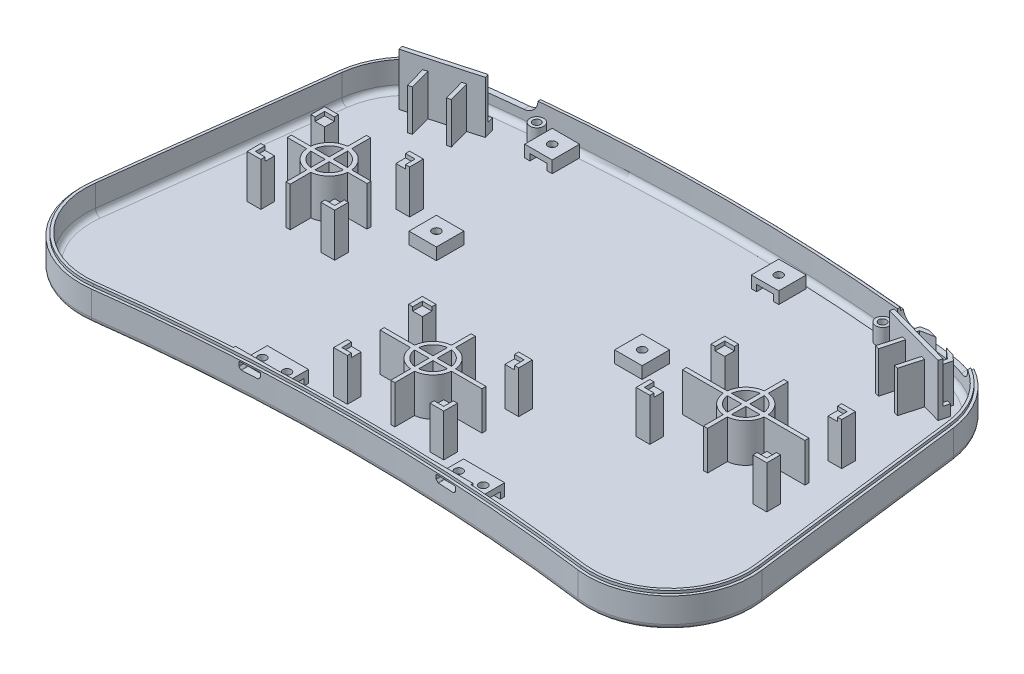
SolidWorks part; units mm, degrees
ref_plane "Plan de face" through (0, 0, 0) normal (0, 0, 1) x (1, 0, 0)
ref_plane "Plan de dessus" through (0, 0, 0) normal (0, 1, 0) x (1, 0, 0)
ref_plane "Plan de droite" through (0, 0, 0) normal (1, 0, 0) x (0, 0, -1)
sketch "Esquisse fond coque" plane through (0, 0, 0) normal (0, 1, 0) x (1, 0, 0)
  line L0 (-122.2671, -38.9175) -> (-112.2671, 40.8662)
  line L1 (112.2671, 40.8662) -> (122.2671, -38.9175)
  line L2 (-103.7302, 58.3314) -> (113.6596, -63.9151) construction
  line L3 (-113.6596, -63.9151) -> (103.7302, 58.3314) construction
  arc A0 (-112.2671, 40.8662) -> (-86.2786, 66.8963) centre (-82.5, 37.1352) cw
  arc A1 (-86.2786, 66.8963) -> (86.2786, 66.8963) centre (0, -612.6484) cw
  arc A2 (86.2786, 66.8963) -> (112.2671, 40.8662) centre (82.5, 37.1352) cw
  arc A3 (-122.2671, -38.9175) -> (-88.6189, -72.3963) centre (-92.5, -42.6484) ccw
  arc A4 (122.2671, -38.9175) -> (88.6189, -72.3963) centre (92.5, -42.6484) cw
  arc A5 (88.6189, -72.3963) -> (-88.6189, -72.3963) centre (0, -751.6398) ccw
  point P14 (122.5, -42.6484)
  point P15 (92.5, -72.6484)
  point P16 (-122.5, -42.6484)
  point P17 (0, 72.3516)
  point P18 (0, -66.6398)
  point P23 (0, 0)
  dimension "D4" = 30
  dimension "D5" = 30
  dimension "D6" = 685
  dimension "D7" = 685
  dimension "D1" = 245
  dimension "D2" = 165
  dimension "D3" = 145
extrude "Fond coque" add sketch "Esquisse fond coque" along normal blind 2
sketch "Esquisse contour coque" plane through (0, 2, 0) normal (0, 1, 0) x (1, 0, 0)
  line L0 (-120.2826, -39.1662) -> (-110.2826, 40.6174)
  line L1 (110.2826, 40.6174) -> (120.2826, -39.1662)
  line L2 (122.2671, -38.9175) -> (112.2671, 40.8662) construction
  line L3 (-112.2671, 40.8662) -> (-122.2671, -38.9175) construction
  line L4 (-122.2671, -38.9175) -> (-112.2671, 40.8662)
  line L5 (112.2671, 40.8662) -> (122.2671, -38.9175)
  arc A0 (-110.2826, 40.6174) -> (-86.0267, 64.9122) centre (-82.5, 37.1352) cw
  arc A1 (-86.0267, 64.9122) -> (86.0267, 64.9122) centre (0, -612.6484) cw
  arc A2 (86.0267, 64.9122) -> (110.2826, 40.6174) centre (82.5, 37.1352) cw
  arc A3 (120.2826, -39.1662) -> (88.8776, -70.4131) centre (92.5, -42.6484) cw
  arc A4 (-120.2826, -39.1662) -> (-88.8776, -70.4131) centre (-92.5, -42.6484) ccw
  arc A5 (-88.8776, -70.4131) -> (88.8776, -70.4131) centre (0, -751.6398) cw
  arc A6 (86.2786, 66.8963) -> (-86.2786, 66.8963) centre (0, -612.6484) ccw construction
  arc A7 (88.6189, -72.3963) -> (-88.6189, -72.3963) centre (0, -751.6398) ccw construction
  arc A8 (-88.6189, -72.3963) -> (-122.2671, -38.9175) centre (-92.5, -42.6484) cw
  arc A9 (-122.2671, -38.9175) -> (-88.6189, -72.3963) centre (-92.5, -42.6484) ccw construction
  arc A10 (88.6189, -72.3963) -> (122.2671, -38.9175) centre (92.5, -42.6484) ccw
  arc A11 (88.6189, -72.3963) -> (122.2671, -38.9175) centre (92.5, -42.6484) ccw construction
  arc A12 (-112.2671, 40.8662) -> (-86.2786, 66.8963) centre (-82.5, 37.1352) cw
  arc A13 (-86.2786, 66.8963) -> (-112.2671, 40.8662) centre (-82.5, 37.1352) ccw construction
  arc A14 (86.2786, 66.8963) -> (112.2671, 40.8662) centre (82.5, 37.1352) cw
  arc A15 (112.2671, 40.8662) -> (86.2786, 66.8963) centre (82.5, 37.1352) ccw construction
  arc A16 (-88.6189, -72.3963) -> (88.6189, -72.3963) centre (0, -751.6398) cw
  arc A17 (-86.2786, 66.8963) -> (86.2786, 66.8963) centre (0, -612.6484) cw
  point P6 (0, 70.3516)
  point P14 (0, -64.6398)
  point P18 (0, 72.3516)
  point P23 (0, -66.6398)
  point P31 (-113.6596, -63.9151)
  point P36 (-113.6596, -63.9151)
  point P37 (0, -66.6398)
  point P39 (113.6596, -63.9151)
  point P45 (113.6596, -63.9151)
  point P54 (-103.7302, 58.3314)
  point P55 (-103.7302, 58.3314)
  point P58 (103.7302, 58.3314)
  point P64 (103.7302, 58.3314)
  point P66 (0, 72.3516)
  dimension "D1" = 2
  dimension "D2" = 2
  dimension "D3" = 2
  dimension "D4" = 2
extrude "Contour coque" add sketch "Esquisse contour coque" along normal blind 10
fillet "Congé1" radius 2 8 edges at (-115.2826, 2, -0.7256) (-102.3148, 2, -56.9183) (0, 2, -70.3516) (102.3148, 2, -56.9183) (115.2826, 2, -0.7256) (112.249, 2, 62.4973) (0, 2, 64.6398) (-112.249, 2, 62.4973)
fillet "Congé2" radius 2 8 edges at (0, 0, 66.6398) (113.6596, 0, 63.9151) (117.2671, 0, -0.9743) (103.7302, 0, -58.3314) (0, 0, -72.3516) (-103.7302, 0, -58.3314) (-117.2671, 0, -0.9743) (-113.6596, 0, 63.9151)
sketch "Esquisse glissières Arduino Due" plane through (0, 2, 0) normal (0, 1, 0) x (1, 0, 0)
  line L4 (23.1981, 13.3602) -> (24.7481, 10.6755)
  line L5 (24.7481, 10.6755) -> (27.8481, 10.6755)
  line L6 (27.8481, 10.6755) -> (29.3981, 13.3602)
  line L10 (-51.7319, 13.3602) -> (-50.1819, 10.6755)
  line L11 (-50.1819, 10.6755) -> (-47.0819, 10.6755)
  line L12 (-47.0819, 10.6755) -> (-45.5319, 13.3602)
  line L13 (-51.8819, 61.8802) -> (-53.4319, 64.5649)
  line L14 (-53.4319, 64.5649) -> (-56.5319, 64.5649)
  line L15 (-56.5319, 64.5649) -> (-58.0819, 61.8802)
  line L19 (30.6681, 61.8802) -> (29.1181, 64.5649)
  line L20 (29.1181, 64.5649) -> (26.0181, 64.5649)
  line L21 (26.0181, 64.5649) -> (24.4681, 61.8802)
  line L25 (-45.5319, 13.3602) -> (-45.5319, 18.3602)
  line L26 (23.1981, 13.3602) -> (23.1981, 18.3602)
  line L27 (-25.6887, 16.0449) -> (-27.2475, 16.0449) [skipped]
  line L28 (-43.7885, 10.3406) -> (-44.5679, 11.6906) [skipped]
  line L29 (-41.86, 30.4587) -> (-42.6394, 29.1087) [skipped]
  line L36 (29.3981, 13.3602) -> (29.3981, 18.3602)
  line L37 (-51.8819, 61.8802) -> (-51.8819, 56.8802)
  line L38 (-58.0819, 61.8802) -> (-58.0819, 56.8802)
  line L39 (24.4681, 61.8802) -> (24.4681, 56.8802)
  line L40 (49.2413, 16.0449) -> (47.6825, 16.0449) [skipped]
  line L41 (-9.0051, 79.8766) -> (-9.7845, 81.2266) [skipped]
  line L42 (72.9294, 99.4972) -> (72.15, 98.1472) [skipped]
  line L43 (-7.7887, 59.1955) -> (-6.2299, 59.1955) [skipped]
  line L44 (-49.1973, 66.53) -> (-48.4179, 67.88) [skipped]
  line L45 (-61.0747, 67.0639) -> (-60.2953, 65.7139) [skipped]
  line L46 (30.6681, 61.8802) -> (30.6681, 56.8802)
  line L47 (-54.9819, 61.8802) -> (27.5681, 61.8802) construction
  line L48 (48.6344, 59.1955) -> (50.1932, 59.1955) [skipped]
  line L49 (58.7941, 110.5957) -> (59.5735, 111.9457) [skipped]
  line L50 (6.7317, 92.6006) -> (7.5112, 91.2506) [skipped]
  line L51 (-48.6319, 13.3602) -> (26.2981, 13.3602) construction
  line L52 (-58.0819, 56.8802) -> (-59.9819, 56.8802)
  line L53 (-51.7319, 13.3602) -> (-51.7319, 18.3602)
  line L54 (-59.9819, 56.8802) -> (-59.9819, 66.8802)
  line L55 (-59.9819, 66.8802) -> (-49.9819, 66.8802)
  line L56 (-49.9819, 66.8802) -> (-49.9819, 56.8802)
  line L57 (-49.9819, 56.8802) -> (-51.8819, 56.8802)
  line L58 (24.4681, 56.8802) -> (22.5681, 56.8802)
  line L59 (22.5681, 56.8802) -> (22.5681, 66.8802)
  line L60 (22.5681, 66.8802) -> (32.5681, 66.8802)
  line L61 (32.5681, 66.8802) -> (32.5681, 56.8802)
  line L62 (32.5681, 56.8802) -> (30.6681, 56.8802)
  line L63 (23.1981, 18.3602) -> (21.2981, 18.3602)
  line L64 (21.2981, 18.3602) -> (21.2981, 8.3602)
  line L65 (21.2981, 8.3602) -> (31.2981, 8.3602)
  line L66 (31.2981, 8.3602) -> (31.2981, 18.3602)
  line L67 (31.2981, 18.3602) -> (29.3981, 18.3602)
  line L68 (-45.5319, 18.3602) -> (-43.6319, 18.3602)
  line L69 (-43.6319, 18.3602) -> (-43.6319, 8.3602)
  line L70 (-43.6319, 8.3602) -> (-53.6319, 8.3602)
  line L71 (-53.6319, 8.3602) -> (-53.6319, 18.3602)
  line L72 (-53.6319, 18.3602) -> (-51.7319, 18.3602)
  arc A0 (89.1364, -68.4299) -> (-89.1364, -68.4299) centre (0, -751.6398) ccw construction
  point P9 (-48.6319, 10.6755)
  point P30 (0, -62.6398)
  dimension "D4" = 5
  dimension "D8" = 5
  dimension "D10" = 5
  dimension "D12" = 5
  dimension "D2" = 1.27
  dimension "D3" = 92
  dimension "D5" = 6.2
  dimension "D6" = 74.93
  dimension "D7" = 3.1
  dimension "D9" = 6.2
  dimension "D11" = 82.55
  dimension "D13" = 76
  dimension "D14" = 6.2
  dimension "D15" = 6.2
  dimension "D16" = 48.52
  dimension "D17" = 10
  dimension "D18" = 10
  dimension "D19" = 10
  dimension "D20" = 10
  dimension "D21" = 10
  dimension "D22" = 10
  dimension "D23" = 10
  dimension "D24" = 10
  dimension "D25" = 10
extrude "Glissières Arduino Due" add sketch "Esquisse glissières Arduino Due" along normal blind 2.35
sketch "Esquisse support Arduino Due" plane through (0, 4.35, 0) normal (0, 1, 0) x (1, 0, 0)
  line L0 (-56.5319, 64.5649) -> (-53.4319, 64.5649) construction
  line L1 (-59.9819, 56.8802) -> (-49.9819, 56.8802)
  line L2 (-59.9819, 56.8802) -> (-59.9819, 66.8802)
  line L3 (-59.9819, 66.8802) -> (-49.9819, 66.8802)
  line L4 (-49.9819, 56.8802) -> (-49.9819, 66.8802)
  line L5 (22.5681, 56.8802) -> (32.5681, 56.8802)
  line L6 (22.5681, 56.8802) -> (22.5681, 66.8802)
  line L7 (22.5681, 66.8802) -> (32.5681, 66.8802)
  line L8 (32.5681, 56.8802) -> (32.5681, 66.8802)
  line L9 (21.2981, 8.3602) -> (31.2981, 8.3602)
  line L10 (21.2981, 8.3602) -> (21.2981, 18.3602)
  line L11 (21.2981, 18.3602) -> (31.2981, 18.3602)
  line L12 (31.2981, 8.3602) -> (31.2981, 18.3602)
  line L13 (-53.6319, 8.3602) -> (-43.6319, 8.3602)
  line L14 (-53.6319, 8.3602) -> (-53.6319, 18.3602)
  line L15 (-53.6319, 18.3602) -> (-43.6319, 18.3602)
  line L16 (-43.6319, 8.3602) -> (-43.6319, 18.3602)
  line L17 (-47.0819, 10.6755) -> (-50.1819, 10.6755) construction
  line L18 (27.8481, 10.6755) -> (24.7481, 10.6755) construction
  line L19 (26.0181, 64.5649) -> (29.1181, 64.5649) construction
  circle A2 centre (26.2981, 13.3602) radius 1.5
  circle A5 centre (27.5681, 61.8802) radius 1.5
  circle A6 centre (-48.6319, 13.3602) radius 1.5
  circle A7 centre (-54.9819, 61.8802) radius 1.5
  point P38 (-54.9819, 64.5649)
  point P41 (-48.6319, 10.6755)
  point P44 (26.2981, 10.6755)
  point P47 (27.5681, 64.5649)
  dimension "D1" = 3
  dimension "D2" = 3
  dimension "D3" = 3
  dimension "D4" = 3
extrude "Support Arduino Due" add sketch "Esquisse support Arduino Due" along normal blind 2
sketch "Esquisse entrée USB Native" plane through (0, 0, 0) normal (0, 0, 1) x (1, 0, 0)
  line L0 (32.925, 8) -> (38.575, 8)
  line L1 (38.7863, 8.087) -> (39.4113, 8.707)
  line L2 (39.5, 8.92) -> (39.5, 10.15)
  line L3 (39.2, 10.45) -> (32.3, 10.45)
  line L4 (32, 10.15) -> (32, 8.92)
  line L5 (32.0887, 8.707) -> (32.7137, 8.087)
  line L7 (-88.6189, 2) -> (88.6189, 2) construction
  arc A0 (38.575, 8) -> (38.7863, 8.087) centre (38.575, 8.3) ccw
  arc A1 (39.4113, 8.707) -> (39.5, 8.92) centre (39.2, 8.92) ccw
  arc A2 (39.5, 10.15) -> (39.2, 10.45) centre (39.2, 10.15) ccw
  arc A3 (32.3, 10.45) -> (32, 10.15) centre (32.3, 10.15) ccw
  arc A4 (32, 8.92) -> (32.0887, 8.707) centre (32.3, 8.92) ccw
  arc A5 (32.7137, 8.087) -> (32.925, 8) centre (32.925, 8.3) ccw
  point P20 (35.75, 8)
  point P42 (35.75, 10.45)
  dimension "D2" = 0.3
  dimension "D3" = 0.3
  dimension "D4" = 0.3
  dimension "D5" = 0.3
  dimension "D6" = 0.3
  dimension "D7" = 0.3
  dimension "D1" = 2.45
  dimension "D8" = 5.65
  dimension "D9" = 0.92
  dimension "D10" = 32
  dimension "D12" = 7.5
  dimension "D13" = 8.45
extrude "Entrée USB Native" cut sketch "Esquisse entrée USB Native" along normal up to next
sketch "Esquisse glissières USB Native" plane through (0, 2, 0) normal (0, 1, 0) x (1, 0, 0)
  line L0 (28.2503, -53.6426) -> (28.2503, -55.2409)
  line L1 (28.2503, -53.6426) -> (43.2503, -53.6426)
  line L2 (43.2503, -53.6426) -> (43.2503, -55.2409)
  line L3 (33.86, -58.3409) -> (37.4406, -58.3409) construction
  line L7 (31.1753, -61.4409) -> (33.86, -59.8909)
  line L8 (33.86, -59.8909) -> (33.86, -56.7909)
  line L9 (33.86, -56.7909) -> (31.1753, -55.2409)
  line L10 (40.1253, -55.2409) -> (37.4406, -56.7909)
  line L11 (37.4406, -56.7909) -> (37.4406, -59.8909)
  line L12 (37.4406, -59.8909) -> (40.1253, -61.4409)
  line L16 (31.1753, -55.2409) -> (28.2503, -55.2409)
  line L17 (31.1753, -61.4409) -> (28.2503, -61.4409)
  line L18 (28.2503, -61.4409) -> (28.2503, -65.2209)
  line L22 (40.1253, -55.2409) -> (43.2503, -55.2409)
  line L23 (40.1253, -61.4409) -> (43.2503, -61.4409)
  line L25 (28.9014, -67.921) -> (30.2437, -67.146) [skipped]
  line L26 (43.2503, -61.4409) -> (43.2503, -66.0026)
  line L27 (42.81, -66.5249) -> (42.81, -64.9749) [skipped]
  line L28 (32.0932, -50.6036) -> (30.7509, -49.8286) [skipped]
  arc A0 (88.8776, -70.4131) -> (-88.8776, -70.4131) centre (0, -751.6398) ccw construction
  arc A2 (88.8776, -70.4131) -> (-88.8776, -70.4131) centre (0, -751.6398) ccw construction
  arc A3 (28.2503, -65.2209) -> (43.2503, -66.0026) centre (0, -751.6398) cw
  arc A5 (38.575, -65.7237) -> (32.925, -65.4292) centre (0, -751.6398) ccw construction
  point P11 (35.7503, -53.6426)
  point P13 (40.1253, -58.3409)
  point P14 (31.1753, -58.3409)
  point P27 (35.6503, -58.3409)
  point P31 (35.7503, -65.5706)
  dimension "D1" = 12.36
  dimension "D2" = 6.88
  dimension "D3" = 6.2
  dimension "D4" = 8.95
  dimension "D5" = 15
  dimension "D6" = 0.1
  dimension "D7" = 0.1
extrude "Glissières USB Native" add sketch "Esquisse glissières USB Native" along normal blind 2.35
sketch "Esquisse support USB Native" plane through (0, 4.35, 0) normal (0, 1, 0) x (1, 0, 0)
  line L0 (28.2503, -53.6426) -> (43.2503, -53.6426)
  line L1 (43.2503, -53.6426) -> (43.2503, -66.0026)
  line L2 (28.2503, -53.6426) -> (28.2503, -65.2209)
  line L3 (33.86, -56.7909) -> (33.86, -59.8909) construction
  line L4 (37.4406, -59.8909) -> (37.4406, -56.7909) construction
  arc A0 (28.2503, -65.2209) -> (43.2503, -66.0026) centre (0, -751.6398) cw
  arc A1 (43.2503, -66.0026) -> (28.2503, -65.2209) centre (0, -751.6398) ccw construction
  circle A2 centre (31.1753, -58.3409) radius 1.5
  circle A3 centre (40.1253, -58.3409) radius 1.5
  point P17 (33.86, -58.3409)
  point P23 (37.4406, -58.3409)
  dimension "D1" = 3
  dimension "D2" = 3
extrude "Support USB Native" add sketch "Esquisse support USB Native" along normal blind 2.05
sketch "Esquisse4" plane through (0, 6.4, 0) normal (0, 1, 0) x (1, 0, 0)
  line L0 (28.2503, -65.2209) -> (43.2503, -65.2209)
  line L1 (43.2503, -66.0026) -> (43.2503, -53.6426) construction
  line L2 (43.2503, -65.2209) -> (43.2503, -66.0026)
  line L6 (28.2503, -53.6426) -> (28.2503, -65.2209)
  line L7 (43.2503, -66.0026) -> (43.2503, -53.6426)
  line L8 (43.2503, -53.6426) -> (28.2503, -53.6426)
  arc A1 (43.2503, -66.0026) -> (28.2503, -65.2209) centre (0, -751.6398) ccw
  arc A2 (43.2503, -66.0026) -> (28.2503, -65.2209) centre (0, -751.6398) ccw
  dimension "D1" = 0
extrude "Boss.-Extru.4" add sketch "Esquisse4" along normal blind 5.6
sketch "Esquisse coins DPad" plane through (0, 2, 0) normal (0, 1, 0) x (1, 0, 0)
  line L0 (-95.2981, 15.8201) -> (-95.2981, 19.3201)
  line L1 (-96.7981, 20.8201) -> (-91.7981, 20.8201)
  line L2 (-96.7981, 20.8201) -> (-96.7981, 15.8201)
  line L3 (-96.7981, 15.8201) -> (-95.2981, 15.8201)
  line L4 (-91.7981, 20.8201) -> (-91.7981, 19.3201)
  line L9 (-96.7981, -2.4299) -> (-95.2981, -2.4299)
  line L10 (-96.7981, -2.4299) -> (-96.7981, -7.4299)
  line L11 (-96.7981, -7.4299) -> (-91.7981, -7.4299)
  line L12 (-91.7981, -5.9299) -> (-91.7981, -7.4299)
  line L13 (-62.2981, -10.0299) -> (-67.2981, -10.0299)
  line L14 (-62.2981, -10.0299) -> (-62.2981, -5.0299)
  line L15 (-62.2981, -5.0299) -> (-63.7981, -5.0299)
  line L16 (-67.2981, -10.0299) -> (-67.2981, -8.5299)
  line L17 (-95.2981, 19.3201) -> (-91.7981, 19.3201)
  line L19 (-62.2981, 22.2701) -> (-67.2981, 22.2701)
  line L20 (-95.2981, -2.4299) -> (-95.2981, -5.9299)
  line L21 (-95.2981, -5.9299) -> (-91.7981, -5.9299)
  line L22 (-63.7981, -5.0299) -> (-63.7981, -8.5299)
  line L23 (-63.7981, -8.5299) -> (-67.2981, -8.5299)
  line L24 (-62.2981, 22.2701) -> (-62.2981, 17.2701)
  line L25 (-62.2981, 17.2701) -> (-63.7981, 17.2701)
  line L26 (-67.2981, 22.2701) -> (-67.2981, 20.7701)
  line L29 (-67.2981, 20.7701) -> (-63.7981, 20.7701)
  line L30 (-63.7981, 17.2701) -> (-63.7981, 20.7701)
  dimension "D2" = 1.5
  dimension "D3" = 1.5
  dimension "D4" = 1.5
  dimension "D5" = 1.5
  dimension "D6" = 1.5
  dimension "D7" = 1.5
  dimension "D8" = 1.5
  dimension "D9" = 1.5
  dimension "D10" = 31.5
  dimension "D11" = 2.6
  dimension "D12" = 5
  dimension "D13" = 5
  dimension "D14" = 5
  dimension "D15" = 5
  dimension "D16" = 5
  dimension "D17" = 5
  dimension "D18" = 1.45
  dimension "D19" = 5
  dimension "D20" = 5
  dimension "D21" = 29.3
  dimension "D22" = 61
  dimension "D23" = 21.5
sketch "Esquisse intérieur DPad" plane through (0, 2, 0) normal (0, 1, 0) x (1, 0, 0)
  line L0 (-91.7981, 15.8201) -> (-67.2981, -5.0299) construction
  line L1 (-95.2981, 19.3201) -> (-91.7981, 19.3201)
  line L2 (-95.2981, 19.3201) -> (-95.2981, 15.8201)
  line L3 (-95.2981, 15.8201) -> (-91.7981, 15.8201)
  line L4 (-91.7981, 19.3201) -> (-91.7981, 15.8201)
  line L5 (-63.7981, 20.7701) -> (-67.2981, 20.7701)
  line L6 (-63.7981, 20.7701) -> (-63.7981, 17.2701)
  line L7 (-63.7981, 17.2701) -> (-67.2981, 17.2701)
  line L8 (-67.2981, 20.7701) -> (-67.2981, 17.2701)
  line L9 (-95.2981, -5.9299) -> (-91.7981, -5.9299)
  line L10 (-95.2981, -5.9299) -> (-95.2981, -2.4299)
  line L11 (-95.2981, -2.4299) -> (-91.7981, -2.4299)
  line L12 (-91.7981, -5.9299) -> (-91.7981, -2.4299)
  line L13 (-63.7981, -8.5299) -> (-67.2981, -8.5299)
  line L14 (-63.7981, -8.5299) -> (-63.7981, -5.0299)
  line L15 (-63.7981, -5.0299) -> (-67.2981, -5.0299)
  line L16 (-67.2981, -8.5299) -> (-67.2981, -5.0299)
  line L21 (-80.0216, 5.6863) -> (-66.2451, 5.6863)
  line L22 (-81.5216, -8.5299) -> (-80.0216, -8.5299)
  line L23 (-91.7981, -2.4299) -> (-67.2981, 17.2701) construction
  line L24 (-81.5216, -8.5299) -> (-81.5216, 5.6863)
  line L25 (-81.5216, 20.7701) -> (-80.0216, 20.7701)
  line L26 (-80.0216, -8.5299) -> (-80.0216, 5.6863)
  line L27 (-81.5216, 7.1863) -> (-80.0216, 7.1863) construction
  line L29 (-95.2981, 7.1863) -> (-81.5216, 7.1863)
  line L30 (-95.2981, 7.1863) -> (-95.2981, 5.6863)
  line L31 (-95.2981, 5.6863) -> (-81.5216, 5.6863)
  line L32 (-66.2451, 7.1863) -> (-66.2451, 5.6863)
  line L33 (-95.2981, 7.1863) -> (-66.2451, 5.6863) construction
  line L34 (-95.2981, 5.6863) -> (-66.2451, 7.1863) construction
  line L35 (-80.0216, 7.1863) -> (-80.0216, 20.7701)
  line L36 (-81.5216, 7.1863) -> (-81.5216, 20.7701)
  line L37 (-80.0216, 7.1863) -> (-66.2451, 7.1863)
  point P24 (-80.7716, 6.4363)
  point P29 (-80.7716, 6.4363)
  point P34 (-80.7716, 6.4363)
  point P39 (-80.7716, 7.1863)
  dimension "D1" = 1.5
  dimension "D2" = 1.5
extrude "Coins DPad" add sketch "Esquisse coins DPad" along normal blind 15.8
extrude "Intérieur DPad" add sketch "Esquisse intérieur DPad" along normal blind 14.4
sketch "Esquisse cercle DPad" plane through (0, 2, 0) normal (0, 1, 0) x (1, 0, 0)
  circle A0 centre (-80.7716, 6.4363) radius 6
  circle A1 centre (-80.7716, 6.4363) radius 7.5
  dimension "D1" = 12
  dimension "D2" = 15
extrude "Cercle DPad" add sketch "Esquisse cercle DPad" along normal blind 14.4
sketch "Esquisse coins ABXY" plane through (0, 2, 0) normal (0, 1, 0) x (1, 0, 0)
  line L1 (48.1981, 16.5851) -> (49.6981, 16.5851)
  line L2 (48.1981, 16.5851) -> (48.1981, 21.5851)
  line L3 (48.1981, 21.5851) -> (53.1981, 21.5851)
  line L4 (53.1981, 20.0851) -> (53.1981, 21.5851)
  line L7 (53.1981, 20.0851) -> (49.6981, 20.0851)
  line L8 (49.6981, 16.5851) -> (49.6981, 20.0851)
  line L9 (94.2981, 16.5851) -> (95.7981, 16.5851)
  line L10 (90.7981, 20.0851) -> (90.7981, 21.5851)
  line L11 (90.7981, 21.5851) -> (95.7981, 21.5851)
  line L12 (95.7981, 16.5851) -> (95.7981, 21.5851)
  line L15 (90.7981, 20.0851) -> (94.2981, 20.0851)
  line L16 (94.2981, 16.5851) -> (94.2981, 20.0851)
  line L17 (49.6981, -5.7149) -> (48.1981, -5.7149)
  line L18 (53.1981, -9.2149) -> (53.1981, -10.7149)
  line L19 (53.1981, -10.7149) -> (48.1981, -10.7149)
  line L20 (48.1981, -5.7149) -> (48.1981, -10.7149)
  line L23 (53.1981, -9.2149) -> (49.6981, -9.2149)
  line L24 (49.6981, -5.7149) -> (49.6981, -9.2149)
  line L25 (94.2981, -5.7149) -> (95.7981, -5.7149)
  line L26 (90.7981, -9.2149) -> (90.7981, -10.7149)
  line L27 (90.7981, -10.7149) -> (95.7981, -10.7149)
  line L28 (95.7981, -5.7149) -> (95.7981, -10.7149)
  line L31 (90.7981, -9.2149) -> (94.2981, -9.2149)
  line L32 (94.2981, -5.7149) -> (94.2981, -9.2149)
  dimension "D1" = 1.5
  dimension "D2" = 1.5
  dimension "D3" = 1.5
  dimension "D4" = 1.5
  dimension "D5" = 1.5
  dimension "D6" = 1.5
  dimension "D7" = 1.5
  dimension "D8" = 1.5
  dimension "D9" = 44.6
  dimension "D10" = 29.3
  dimension "D11" = 5
  dimension "D12" = 5
  dimension "D13" = 5
  dimension "D14" = 5
  dimension "D15" = 57.715
  dimension "D16" = 5
  dimension "D17" = 5
  dimension "D18" = 5
  dimension "D19" = 22.5
  dimension "D20" = 5
extrude "Coins ABXY" add sketch "Esquisse coins ABXY" along normal blind 15.5
sketch "Esquisse intérieur ABXY" plane through (0, 2, 0) normal (0, 1, 0) x (1, 0, 0)
  line L0 (53.1981, 20.0851) -> (53.1981, 21.5851) construction
  line L1 (49.6981, 20.0851) -> (53.1981, 20.0851)
  line L2 (49.6981, 20.0851) -> (49.6981, 16.5851)
  line L3 (49.6981, 16.5851) -> (53.1981, 16.5851)
  line L4 (53.1981, 20.0851) -> (53.1981, 16.5851)
  line L5 (94.2981, 20.0851) -> (90.7981, 20.0851)
  line L6 (94.2981, 20.0851) -> (94.2981, 16.5851)
  line L7 (94.2981, 16.5851) -> (90.7981, 16.5851)
  line L8 (90.7981, 20.0851) -> (90.7981, 16.5851)
  line L9 (49.6981, -9.2149) -> (53.1981, -9.2149)
  line L10 (49.6981, -9.2149) -> (49.6981, -5.7149)
  line L11 (49.6981, -5.7149) -> (53.1981, -5.7149)
  line L12 (53.1981, -9.2149) -> (53.1981, -5.7149)
  line L13 (94.2981, -9.2149) -> (90.7981, -9.2149)
  line L14 (94.2981, -9.2149) -> (94.2981, -5.7149)
  line L15 (94.2981, -5.7149) -> (90.7981, -5.7149)
  line L16 (90.7981, -9.2149) -> (90.7981, -5.7149)
  line L17 (48.1981, 16.5851) -> (49.6981, 16.5851) construction
  line L18 (90.7981, 20.0851) -> (90.7981, 21.5851) construction
  line L19 (94.2981, 16.5851) -> (95.7981, 16.5851) construction
  line L20 (72.7481, 4.6851) -> (94.2981, 4.6851)
  line L21 (94.2981, -5.7149) -> (95.7981, -5.7149) construction
  line L22 (90.7981, -9.2149) -> (90.7981, -10.7149) construction
  line L23 (53.1981, -9.2149) -> (53.1981, -10.7149) construction
  line L24 (49.6981, -5.7149) -> (48.1981, -5.7149) construction
  line L25 (49.6981, 20.0851) -> (94.2981, -9.2149) construction
  line L30 (72.7481, -9.2149) -> (71.2481, -9.2149)
  line L31 (72.7481, -9.2149) -> (72.7481, 4.6851)
  line L32 (94.2981, 20.0851) -> (49.6981, -9.2149) construction
  line L33 (72.7481, 20.0851) -> (71.2481, 20.0851)
  line L34 (71.2481, -9.2149) -> (71.2481, 4.6851)
  line L35 (72.7481, -9.2149) -> (71.2481, 20.0851) construction
  line L36 (72.7481, 20.0851) -> (71.2481, -9.2149) construction
  line L37 (49.6981, 4.6851) -> (71.2481, 4.6851)
  line L38 (49.6981, 4.6851) -> (49.6981, 6.1851)
  line L39 (49.6981, 6.1851) -> (71.2481, 6.1851)
  line L40 (94.2981, 4.6851) -> (94.2981, 6.1851)
  line L41 (49.6981, 4.6851) -> (94.2981, 6.1851) construction
  line L42 (49.6981, 6.1851) -> (94.2981, 4.6851) construction
  line L43 (71.2481, 6.1851) -> (71.2481, 20.0851)
  line L44 (72.7481, 6.1851) -> (94.2981, 6.1851)
  line L45 (72.7481, 6.1851) -> (72.7481, 20.0851)
  point P36 (71.9981, 5.4351)
  point P37 (71.9981, 5.4351)
  point P41 (71.9981, 5.4351)
  point P43 (71.9981, 5.4351)
  dimension "D1" = 1.5
  dimension "D2" = 1.5
extrude "Intérieur ABXY" add sketch "Esquisse intérieur ABXY" along normal blind 14.1
sketch "Esquisse cercle ABXY" plane through (0, 2, 0) normal (0, 1, 0) x (1, 0, 0)
  circle A0 centre (71.9981, 5.4351) radius 6
  circle A1 centre (71.9981, 5.4351) radius 7.5
  dimension "D1" = 12
  dimension "D2" = 15
extrude "Cercle ABXY" add sketch "Esquisse cercle ABXY" along normal blind 14.1
sketch "Esquisse1" plane through (0, 2, 0) normal (0, 1, 0) x (1, 0, 0)
  line L0 (-18.05, -22.35) -> (19.05, -51.65) construction
  line L1 (-19.55, -20.85) -> (-14.55, -20.85)
  line L2 (-19.55, -20.85) -> (-19.55, -25.85)
  line L3 (-19.55, -25.85) -> (-18.05, -25.85)
  line L4 (-14.55, -20.85) -> (-14.55, -22.35)
  line L5 (15.55, -20.85) -> (20.55, -20.85)
  line L6 (15.55, -20.85) -> (15.55, -22.35)
  line L7 (19.05, -25.85) -> (20.55, -25.85)
  line L8 (20.55, -20.85) -> (20.55, -25.85)
  line L9 (-19.55, -53.15) -> (-14.55, -53.15)
  line L10 (-19.55, -53.15) -> (-19.55, -48.15)
  line L11 (-19.55, -48.15) -> (-18.05, -48.15)
  line L12 (-14.55, -53.15) -> (-14.55, -51.65)
  line L13 (20.55, -53.15) -> (15.55, -53.15)
  line L14 (20.55, -53.15) -> (20.55, -48.15)
  line L15 (20.55, -48.15) -> (19.05, -48.15)
  line L16 (15.55, -53.15) -> (15.55, -51.65)
  line L19 (-14.55, -51.65) -> (-18.05, -51.65)
  line L20 (-18.05, -48.15) -> (-18.05, -51.65)
  line L23 (-14.55, -22.35) -> (-18.05, -22.35)
  line L24 (-18.05, -25.85) -> (-18.05, -22.35)
  line L27 (15.55, -22.35) -> (19.05, -22.35)
  line L28 (19.05, -25.85) -> (19.05, -22.35)
  line L31 (15.55, -51.65) -> (19.05, -51.65)
  line L32 (19.05, -48.15) -> (19.05, -51.65)
  line L33 (-18.05, -51.65) -> (19.05, -22.35) construction
  point P1 (0.5, -37)
  dimension "D1" = 1.5
  dimension "D2" = 1.5
  dimension "D3" = 1.5
  dimension "D4" = 1.5
  dimension "D5" = 1.5
  dimension "D6" = 1.5
  dimension "D7" = 1.5
  dimension "D8" = 1.5
  dimension "D9" = 37.1
  dimension "D10" = 29.3
  dimension "D11" = 5
  dimension "D12" = 5
  dimension "D13" = 5
  dimension "D14" = 5
  dimension "D15" = 5
  dimension "D16" = 5
  dimension "D17" = 5
  dimension "D18" = 5
  dimension "D19" = 37
  dimension "D20" = 0.5
sketch "Esquisse2" plane through (0, 2, 0) normal (0, 1, 0) x (1, 0, 0)
  line L0 (-19.55, -25.85) -> (-18.05, -25.85) construction
  line L1 (-18.05, -22.35) -> (-14.55, -22.35)
  line L2 (-18.05, -22.35) -> (-18.05, -25.85)
  line L3 (-18.05, -25.85) -> (-14.55, -25.85)
  line L4 (-14.55, -22.35) -> (-14.55, -25.85)
  line L5 (-19.55, -48.15) -> (-18.05, -48.15) construction
  line L6 (-14.55, -48.15) -> (-18.05, -48.15)
  line L7 (-14.55, -48.15) -> (-14.55, -51.65)
  line L8 (-14.55, -51.65) -> (-18.05, -51.65)
  line L9 (-18.05, -48.15) -> (-18.05, -51.65)
  line L10 (-14.55, -53.15) -> (-14.55, -51.65) construction
  line L11 (15.55, -20.85) -> (15.55, -22.35) construction
  line L12 (19.05, -22.35) -> (15.55, -22.35)
  line L13 (19.05, -22.35) -> (19.05, -25.85)
  line L14 (19.05, -25.85) -> (15.55, -25.85)
  line L15 (15.55, -22.35) -> (15.55, -25.85)
  line L16 (19.05, -25.85) -> (20.55, -25.85) construction
  line L17 (20.55, -48.15) -> (19.05, -48.15) construction
  line L18 (19.05, -51.65) -> (15.55, -51.65)
  line L19 (19.05, -51.65) -> (19.05, -48.15)
  line L20 (19.05, -48.15) -> (15.55, -48.15)
  line L21 (15.55, -51.65) -> (15.55, -48.15)
  line L22 (-14.55, -25.85) -> (15.55, -48.15) construction
  line L23 (-14.55, -48.15) -> (15.55, -25.85) construction
  line L24 (-0.25, -36.25) -> (-0.25, -22.35)
  line L25 (1.25, -51.65) -> (-0.25, -51.65)
  line L26 (1.25, -51.65) -> (1.25, -37.75)
  line L27 (1.25, -22.35) -> (-0.25, -22.35)
  line L28 (-0.25, -51.65) -> (-0.25, -37.75)
  line L29 (1.25, -51.65) -> (-0.25, -22.35) construction
  line L30 (1.25, -22.35) -> (-0.25, -51.65) construction
  line L31 (-18.05, -37.75) -> (-0.25, -37.75)
  line L32 (-18.05, -37.75) -> (-18.05, -36.25)
  line L33 (-18.05, -36.25) -> (-0.25, -36.25)
  line L34 (19.05, -37.75) -> (19.05, -36.25)
  line L35 (-18.05, -37.75) -> (19.05, -36.25) construction
  line L36 (-18.05, -36.25) -> (19.05, -37.75) construction
  line L38 (1.25, -36.25) -> (19.05, -36.25)
  line L39 (1.25, -36.25) -> (1.25, -22.35)
  line L42 (1.25, -37.75) -> (19.05, -37.75)
  point P33 (0.5, -37)
  point P34 (0.5, -37)
  point P39 (0.5, -37)
  dimension "D1" = 1.5
  dimension "D2" = 1.5
extrude "Boss.-Extru.1" add sketch "Esquisse1" along normal blind 15.4
extrude "Boss.-Extru.2" add sketch "Esquisse2" along normal blind 14
sketch "Esquisse3" plane through (0, 2, 0) normal (0, 1, 0) x (1, 0, 0)
  circle A0 centre (0.5, -37) radius 6
  circle A1 centre (0.5, -37) radius 7.5
  dimension "D1" = 12
  dimension "D2" = 15
extrude "Boss.-Extru.3" add sketch "Esquisse3" along normal blind 14
sketch3d "Esquisse3D1"
  point P0 (35.9113, 9.0529, 65.579)
ref_plane "Plan1" through (0, 0, 65.579) normal (0, 0, 1) x (1, 0, 0)
sketch "Esquisse5" plane through (0, 0, 65.579) normal (0, 0, 1) x (1, 0, 0)
  line L0 (32.3, 10.45) -> (39.2, 10.45)
  line L1 (32.3, 10.45) -> (39.2, 10.45) construction
  line L2 (32, 10.15) -> (32, 8.92)
  line L3 (32.0887, 8.707) -> (32.7137, 8.087)
  line L4 (32.925, 8) -> (38.575, 8)
  line L5 (38.575, 8) -> (32.925, 8) construction
  line L6 (38.7863, 8.087) -> (39.4113, 8.707)
  line L7 (39.5, 8.92) -> (39.5, 10.15)
  arc A0 (32.3, 10.45) -> (32, 10.15) centre (32.3, 10.15) ccw
  arc A1 (32.3, 10.45) -> (32, 10.15) centre (32.3, 10.15) ccw construction
  arc A2 (32, 8.92) -> (32.0887, 8.707) centre (32.3, 8.92) ccw
  arc A3 (32, 8.92) -> (32.0887, 8.707) centre (32.3, 8.92) ccw construction
  arc A4 (32.7137, 8.087) -> (32.925, 8) centre (32.925, 8.3) ccw
  arc A5 (32.7137, 8.087) -> (32.925, 8) centre (32.925, 8.3) ccw construction
  arc A6 (38.575, 8) -> (38.7863, 8.087) centre (38.575, 8.3) ccw
  arc A7 (38.575, 8) -> (38.7863, 8.087) centre (38.575, 8.3) ccw construction
  arc A8 (39.4113, 8.707) -> (39.5, 8.92) centre (39.2, 8.92) ccw
  arc A9 (39.2, 10.45) -> (39.5, 10.15) centre (39.2, 10.15) cw
  arc A10 (39.5, 10.15) -> (39.2, 10.45) centre (39.2, 10.15) ccw construction
extrude "Enlèv. mat.-Extru.1" cut sketch "Esquisse5" against normal mid plane 2
sketch "Esquisse6" plane through (0, 0, 0) normal (0, 0, 1) x (1, 0, 0)
  line L0 (-38.575, 8) -> (-32.925, 8)
  line L1 (-32.7137, 8.087) -> (-32.0887, 8.707)
  line L2 (-32, 8.92) -> (-32, 10.15)
  line L3 (-32.3, 10.45) -> (-39.2, 10.45)
  line L4 (-39.5, 10.15) -> (-39.5, 8.92)
  line L5 (-39.4113, 8.707) -> (-38.7863, 8.087)
  line L6 (32.3, 10.45) -> (39.2, 10.45) construction
  arc A0 (-32.925, 8) -> (-32.7137, 8.087) centre (-32.925, 8.3) ccw
  arc A1 (-32.0887, 8.707) -> (-32, 8.92) centre (-32.3, 8.92) ccw
  arc A2 (-32, 10.15) -> (-32.3, 10.45) centre (-32.3, 10.15) ccw
  arc A3 (-39.2, 10.45) -> (-39.5, 10.15) centre (-39.2, 10.15) ccw
  arc A4 (-39.5, 8.92) -> (-39.4113, 8.707) centre (-39.2, 8.92) ccw
  arc A5 (-38.7863, 8.087) -> (-38.575, 8) centre (-38.575, 8.3) ccw
  point P20 (-35.75, 8)
  point P42 (-35.75, 10.45)
  dimension "D2" = 0.3
  dimension "D3" = 0.3
  dimension "D4" = 0.3
  dimension "D5" = 0.3
  dimension "D6" = 0.3
  dimension "D7" = 0.3
  dimension "D1" = 2.45
  dimension "D8" = 5.65
  dimension "D9" = 0.92
  dimension "D10" = 39.5
  dimension "D12" = 7.5
extrude "Enlèv. mat.-Extru.2" cut sketch "Esquisse6" along normal up to next
sketch "Esquisse11" plane through (0, 2, 0) normal (0, 1, 0) x (1, 0, 0)
  line L0 (-43.2503, -66.0026) -> (-43.2503, -61.4409)
  line L1 (-43.2503, -53.6426) -> (-28.2503, -53.6426)
  line L2 (-28.2503, -53.6426) -> (-28.2503, -55.2409)
  line L3 (43.2503, -53.6426) -> (28.2503, -53.6426) construction
  line L6 (-43.2503, -55.2409) -> (-40.3253, -55.2409)
  line L7 (-40.3253, -55.2409) -> (-37.6406, -56.7909)
  line L8 (-37.6406, -56.7909) -> (-37.6406, -59.8909)
  line L9 (-37.6406, -59.8909) -> (-40.3253, -61.4409)
  line L10 (-40.3253, -61.4409) -> (-43.2503, -61.4409)
  line L11 (-28.2503, -55.2409) -> (-31.3753, -55.2409)
  line L12 (-31.3753, -55.2409) -> (-34.06, -56.7909)
  line L13 (-34.06, -56.7909) -> (-34.06, -59.8909)
  line L14 (-34.06, -59.8909) -> (-31.3753, -61.4409)
  line L15 (-31.3753, -61.4409) -> (-28.2503, -61.4409)
  line L16 (28.2503, -55.2409) -> (31.1753, -55.2409) construction
  line L17 (31.1753, -61.4409) -> (28.2503, -61.4409) construction
  line L18 (-43.2503, -55.2409) -> (-43.2503, -53.6426)
  line L19 (-43.2503, -55.2409) -> (-43.2503, -61.4409) construction
  line L20 (40.1253, -55.2409) -> (43.2503, -55.2409) construction
  line L21 (-28.2503, -61.4409) -> (-28.2503, -65.2209)
  line L22 (-37.6406, -58.3409) -> (-34.06, -58.3409) construction
  arc A0 (28.2503, -65.2209) -> (-88.8776, -70.4131) centre (0, -751.6398) ccw construction
  arc A1 (-32.925, -65.4292) -> (-38.575, -65.7237) centre (0, -751.6398) ccw construction
  arc A4 (-43.2503, -66.0026) -> (-28.2503, -65.2209) centre (0, -751.6398) cw
  point P10 (-35.8503, -58.3409)
  point P28 (-37.6406, -58.3409)
  point P29 (-43.2503, -58.3409)
  point P33 (-34.06, -58.3409)
  point P34 (-35.7503, -65.5706)
  point P35 (-40.3253, -58.3409)
  point P38 (-31.3753, -58.3409)
  dimension "D1" = 3.1
  dimension "D2" = 0.1
extrude "Boss.-Extru.10" add sketch "Esquisse11" along normal blind 2.35
sketch "Esquisse12" plane through (0, 4.35, 0) normal (0, 1, 0) x (1, 0, 0)
  line L0 (-28.2503, -53.6426) -> (-43.2503, -53.6426)
  line L1 (-43.2503, -53.6426) -> (-43.2503, -66.0026)
  line L2 (-28.2503, -53.6426) -> (-28.2503, -65.2209)
  line L3 (-37.6406, -56.7909) -> (-37.6406, -59.8909) construction
  line L4 (-34.06, -59.8909) -> (-34.06, -56.7909) construction
  arc A0 (-43.2503, -66.0026) -> (-28.2503, -65.2209) centre (0, -751.6398) cw
  arc A1 (-28.2503, -65.2209) -> (-43.2503, -66.0026) centre (0, -751.6398) ccw construction
  circle A2 centre (-40.3253, -58.3409) radius 1.5
  circle A3 centre (-31.3753, -58.3409) radius 1.5
  point P20 (-37.6406, -58.3409)
  point P24 (-34.06, -58.3409)
  dimension "D1" = 3
  dimension "D2" = 3
extrude "Boss.-Extru.11" add sketch "Esquisse12" along normal blind 2.05
sketch "Esquisse13" plane through (0, 6.4, 0) normal (0, 1, 0) x (1, 0, 0)
  line L0 (-28.2503, -65.2209) -> (-43.2503, -65.2209)
  line L1 (-43.2503, -53.6426) -> (-43.2503, -66.0026) construction
  line L2 (-43.2503, -65.2209) -> (-43.2503, -66.0026)
  arc A0 (-43.2503, -66.0026) -> (-28.2503, -65.2209) centre (0, -751.6398) cw
  arc A1 (-28.2503, -65.2209) -> (-43.2503, -66.0026) centre (0, -751.6398) ccw construction
extrude "Boss.-Extru.12" add sketch "Esquisse13" along normal blind 5.6
sketch3d "Esquisse3D2"
  point P0 (-36.686, 9.3155, 65.62)
ref_plane "Plan2" through (0, 0, 65.62) normal (0, 0, 1) x (1, 0, 0)
sketch "Esquisse15" plane through (0, 0, 65.62) normal (0, 0, 1) x (1, 0, 0)
  line L0 (-39.2, 10.45) -> (-32.3, 10.45)
  line L1 (-39.5, 8.92) -> (-39.5, 10.15) construction
  line L2 (-39.5, 10.15) -> (-39.5, 8.92)
  line L3 (-39.4113, 8.707) -> (-38.7863, 8.087)
  line L4 (-38.575, 8) -> (-32.925, 8)
  line L5 (-32, 10.15) -> (-32, 8.92) construction
  line L6 (-32.7137, 8.087) -> (-32.0887, 8.707)
  line L7 (-32, 8.92) -> (-32, 10.15)
  line L8 (-39.2, 10.45) -> (-32.3, 10.45) construction
  line L9 (-32.925, 8) -> (-38.575, 8) construction
  line L10 (-38.7863, 8.087) -> (-39.4113, 8.707) construction
  line L11 (-32.0887, 8.707) -> (-32.7137, 8.087) construction
  arc A0 (-39.2, 10.45) -> (-39.5, 10.15) centre (-39.2, 10.15) ccw
  arc A1 (-39.5, 8.92) -> (-39.4113, 8.707) centre (-39.2, 8.92) ccw construction
  arc A2 (-39.5, 8.92) -> (-39.4113, 8.707) centre (-39.2, 8.92) ccw
  arc A3 (-38.7863, 8.087) -> (-38.575, 8) centre (-38.575, 8.3) ccw construction
  arc A4 (-38.7863, 8.087) -> (-38.575, 8) centre (-38.575, 8.3) ccw
  arc A5 (-32.925, 8) -> (-32.7137, 8.087) centre (-32.925, 8.3) ccw construction
  arc A6 (-32.925, 8) -> (-32.7137, 8.087) centre (-32.925, 8.3) ccw
  arc A7 (-32.0887, 8.707) -> (-32, 8.92) centre (-32.3, 8.92) ccw construction
  arc A8 (-32.0887, 8.707) -> (-32, 8.92) centre (-32.3, 8.92) ccw
  arc A9 (-32.3, 10.45) -> (-32, 10.15) centre (-32.3, 10.15) cw
  arc A10 (-32, 10.15) -> (-32.3, 10.45) centre (-32.3, 10.15) ccw construction
  arc A11 (-39.2, 10.45) -> (-39.5, 10.15) centre (-39.2, 10.15) ccw construction
extrude "Enlèv. mat.-Extru.3" cut sketch "Esquisse15" against normal mid plane 2
sketch3d "Esquisse3D3"
  point P0 (78.6551, 10.1841, -67.8208)
ref_plane "Plan3" through (0, 0, -67.8208) normal (0, 0, -1) x (-1, 0, 0)
sketch "Esquisse24" plane through (0, 0, -67.8208) normal (0, 0, -1) x (-1, 0, 0)
  line L0 (-92.85, 12) -> (-70.15, 12) construction
  line L1 (-86.2786, 12) -> (-112.2671, 12) construction
  line L3 (-92.85, 7.35) -> (-70.15, 7.35)
  line L5 (-97.5, 12) -> (-65.5, 12)
  line L6 (-122.5, 12) -> (-122.5, 2) construction
  line L7 (97.5, 12) -> (65.5, 12)
  line L8 (112.2671, 12) -> (86.2786, 12) construction
  line L11 (70.15, 7.35) -> (92.85, 7.35)
  line L13 (86.2786, 12) -> (-86.2786, 12) construction
  line L14 (122.5, 2) -> (122.5, 12) construction
  arc A0 (-97.5, 12) -> (-92.85, 7.35) centre (-92.85, 12) ccw
  arc A1 (-70.15, 7.35) -> (-65.5, 12) centre (-70.15, 12) ccw
  arc A2 (65.5, 12) -> (70.15, 7.35) centre (70.15, 12) ccw
  arc A3 (97.5, 12) -> (92.85, 7.35) centre (92.85, 12) cw
  point P4 (-92.8, 12)
  dimension "D1" = 4.65
  dimension "D2" = 32
  dimension "D3" = 25
  dimension "D4" = 32
  dimension "D5" = 25
extrude "Enlèv. mat.-Extru.5" cut sketch "Esquisse24" against normal mid plane 25
sketch "Esquisse25" plane through (0, 2, 0) normal (0, 1, 0) x (1, 0, 0)
  line L0 (65.5, 67.2036) -> (65.5, 69.2128) construction
  circle A0 centre (-62.98, 64.3036) radius 2.5
  circle A1 centre (-62.98, 64.3036) radius 1.4
  circle A2 centre (62.98, 64.3036) radius 2.5
  circle A3 centre (62.98, 64.3036) radius 1.4
  dimension "D1" = 5
  dimension "D2" = 2.8
  dimension "D5" = 2.8
  dimension "D6" = 5
  dimension "D3" = 2.9
  dimension "D4" = 2.52
  dimension "D7" = 2.9
  dimension "D8" = 2.52
extrude "Boss.-Extru.19" add sketch "Esquisse25" along normal blind 6.04
sketch "Esquisse26" plane through (0, 2, 0) normal (0, 1, 0) x (1, 0, 0)
  line L0 (-91.5965, 54.4463) -> (-95.1615, 53.4559)
  line L1 (-95.1615, 53.4559) -> (-96.1334, 56.9548)
  line L2 (-96.1334, 56.9548) -> (-94.386, 58.2313)
  line L3 (-94.386, 58.2313) -> (-90.5564, 59.2952)
  line L4 (-90.5564, 59.2952) -> (-94.4389, 56.4589)
  line L5 (-94.4389, 56.4589) -> (-94.0909, 55.2064)
  line L6 (-94.0909, 55.2064) -> (-91.9712, 55.7952)
  line L7 (-91.9712, 55.7952) -> (-91.5965, 54.4463)
  line L8 (-85.2571, 60.7674) -> (-81.4275, 61.8313)
  line L9 (-81.4275, 61.8313) -> (-79.272, 61.6389)
  line L10 (-79.272, 61.6389) -> (-78.3, 58.1401)
  line L11 (-78.3, 58.1401) -> (-81.865, 57.1497)
  line L12 (-81.865, 57.1497) -> (-82.2397, 58.4987)
  line L13 (-82.2397, 58.4987) -> (-80.12, 59.0875)
  line L14 (-80.12, 59.0875) -> (-80.468, 60.3401)
  line L15 (-80.468, 60.3401) -> (-85.2571, 60.7674)
  line L16 (81.865, 57.1497) -> (78.3, 58.1401)
  line L17 (78.3, 58.1401) -> (79.2733, 61.6437)
  line L18 (79.2733, 61.6437) -> (82.102, 62.1695)
  line L19 (82.102, 62.1695) -> (85.3926, 61.2553)
  line L20 (85.3926, 61.2553) -> (80.468, 60.3401)
  line L21 (80.468, 60.3401) -> (80.12, 59.0875)
  line L22 (80.12, 59.0875) -> (82.2397, 58.4987)
  line L23 (82.2397, 58.4987) -> (81.865, 57.1497)
  line L24 (90.6919, 59.7831) -> (93.9826, 58.869)
  line L25 (93.9826, 58.869) -> (96.1348, 56.9596)
  line L26 (96.1348, 56.9596) -> (95.1615, 53.4559)
  line L27 (95.1615, 53.4559) -> (91.5965, 54.4463)
  line L28 (91.5965, 54.4463) -> (91.9712, 55.7952)
  line L29 (91.9712, 55.7952) -> (94.0909, 55.2064)
  line L30 (94.0909, 55.2064) -> (94.4389, 56.4589)
  line L31 (94.4389, 56.4589) -> (90.6919, 59.7831)
  line L33 (97.5, 60.7784) -> (97.5, 63.1159) construction
  dimension "D1" = 1.4
  dimension "D2" = 1.5
  dimension "D3" = 1.4
  dimension "D4" = 1.5
  dimension "D5" = 1.4
  dimension "D6" = 1.4
  dimension "D7" = 1.3
  dimension "D8" = 2.2
  dimension "D9" = 2.2
  dimension "D10" = 14.5
  dimension "D11" = 3.5
  dimension "D12" = 6
  dimension "D13" = 6
  dimension "D14" = 10.61
  dimension "D15" = 9.66
  dimension "D16" = 19.2
  dimension "D17" = 1.4
  dimension "D18" = 1.5
  dimension "D19" = 1.5
  dimension "D20" = 1.5
  dimension "D21" = 1.4
  dimension "D22" = 1.5
  dimension "D23" = 2.2
  dimension "D24" = 2.2
  dimension "D25" = 14.5
  dimension "D26" = 3.5
  dimension "D27" = 6
  dimension "D28" = 10.61
  dimension "D29" = 9.66
  dimension "D30" = 6
  dimension "D31" = 1.3
  dimension "D32" = 19.2
extrude "Boss.-Extru.20" add sketch "Esquisse26" along normal blind 14
sketch "Esquisse27" plane through (0, 2, 0) normal (0, 1, 0) x (1, 0, 0)
  line L0 (-89.7535, 59.5183) -> (-88.5775, 55.285)
  line L1 (-88.5775, 55.285) -> (-87.1322, 55.6865)
  line L2 (-87.1322, 55.6865) -> (-88.3082, 59.9198)
  line L3 (-88.3082, 59.9198) -> (-89.7535, 59.5183)
  line L4 (-87.5053, 60.1428) -> (-86.3293, 55.9095)
  line L5 (-86.3293, 55.9095) -> (-84.884, 56.311)
  line L6 (-84.884, 56.311) -> (-86.06, 60.5443)
  line L7 (-87.5053, 60.1428) -> (-86.06, 60.5443)
  line L8 (-91.5965, 54.4463) -> (-91.9712, 55.7952) construction
  line L9 (-95.1615, 53.4559) -> (-91.5965, 54.4463) construction
  line L10 (-90.5564, 59.2952) -> (-94.386, 58.2313) construction
  line L11 (-90.5564, 59.2952) -> (-89.7535, 59.5183) construction
  line L12 (-88.3082, 59.9198) -> (-87.5053, 60.1428) construction
  line L13 (-85.2571, 60.7674) -> (-86.06, 60.5443) construction
  line L14 (-85.2571, 60.7674) -> (-80.468, 60.3401) construction
  line L15 (84.884, 56.311) -> (86.1956, 61.0323)
  line L16 (86.1956, 61.0323) -> (87.6408, 60.6308)
  line L17 (87.6408, 60.6308) -> (86.3293, 55.9095)
  line L18 (86.3293, 55.9095) -> (84.884, 56.311)
  line L19 (87.1322, 55.6865) -> (88.5775, 55.285)
  line L20 (88.5775, 55.285) -> (89.889, 60.0062)
  line L21 (89.889, 60.0062) -> (88.4438, 60.4077)
  line L22 (88.4438, 60.4077) -> (87.1322, 55.6865)
  line L23 (81.865, 57.1497) -> (82.2397, 58.4987) construction
  line L24 (85.3926, 61.2553) -> (82.102, 62.1695) construction
  line L25 (78.3, 58.1401) -> (81.865, 57.1497) construction
  line L26 (78.3, 58.1401) -> (81.865, 57.1497) construction
  line L27 (85.3926, 61.2553) -> (86.1956, 61.0323) construction
  line L28 (87.6408, 60.6308) -> (88.4438, 60.4077) construction
  line L29 (90.6919, 59.7831) -> (89.889, 60.0062) construction
  dimension "D1" = 1.5
  dimension "D2" = 1.5
  dimension "D3" = 1.5
  dimension "D4" = 1.5
extrude "Boss.-Extru.21" add sketch "Esquisse27" along normal blind 3.85
sketch "Esquisse28" plane through (-20.6042, 0, -74.1682) normal (0.2677, 0, 0.9635) x (0.9635, 0, -0.2677)
  line L0 (-73.6808, 16) -> (-73.6808, 2) construction
  line L1 (-63.5808, 16) -> (-63.5808, 2) construction
  circle A0 centre (-68.6308, 12) radius 5.05
sketch "Esquisse29" plane through (20.6042, 0, -74.1682) normal (-0.2677, 0, 0.9635) x (0.9635, 0, 0.2677)
  line L0 (73.6808, 16) -> (73.6808, 2) construction
  line L1 (63.5808, 16) -> (63.5808, 2) construction
  circle A0 centre (68.6308, 12) radius 5.05
sketch "Esquisse31" plane through (0, 2, 0) normal (0, 1, 0) x (1, 0, 0)
  line L0 (78.3, 58.1401) -> (75.8912, 58.8093) construction
  line L1 (75.8912, 58.8093) -> (75.4362, 57.1713) construction
  line L2 (75.4362, 57.1713) -> (97.1152, 51.1488) construction
  line L3 (95.1615, 53.4559) -> (97.5702, 52.7868) construction
  line L4 (97.5702, 52.7868) -> (97.1152, 51.1488) construction
  line L5 (78.3, 58.1401) -> (81.865, 57.1497) construction
  line L6 (91.5965, 54.4463) -> (95.1615, 53.4559) construction
  line L7 (79.2733, 61.6437) -> (78.3, 58.1401) construction
  line L8 (75.4362, 57.1713) -> (97.1152, 51.1488)
  line L10 (98.159, 49.302) -> (73.5894, 56.1275)
  line L13 (73.5894, 56.1275) -> (74.5798, 59.6925)
  line L14 (74.5798, 59.6925) -> (76.0251, 59.291)
  line L15 (76.0251, 59.291) -> (75.4362, 57.1713)
  line L16 (79.2733, 61.6437) -> (78.3, 58.1401) construction
  line L18 (98.159, 49.302) -> (99.1493, 52.867)
  line L19 (99.1493, 52.867) -> (97.7041, 53.2685)
  line L20 (97.7041, 53.2685) -> (97.1152, 51.1488)
  line L21 (95.1615, 53.4559) -> (96.1348, 56.9596) construction
  line L22 (-97.7041, 53.2685) -> (-97.1152, 51.1488)
  line L23 (-97.1152, 51.1488) -> (-75.4362, 57.1713)
  line L24 (-75.4362, 57.1713) -> (-76.0251, 59.291)
  line L25 (-76.0251, 59.291) -> (-74.5798, 59.6925)
  line L26 (-74.5798, 59.6925) -> (-73.5894, 56.1275)
  line L27 (-73.5894, 56.1275) -> (-98.159, 49.302)
  line L28 (-98.159, 49.302) -> (-99.1493, 52.867)
  line L29 (-99.1493, 52.867) -> (-97.7041, 53.2685)
  line L31 (-96.1334, 56.9548) -> (-95.1615, 53.4559) construction
  line L32 (-95.1615, 53.4559) -> (-91.5965, 54.4463) construction
  line L33 (-78.3, 58.1401) -> (-79.272, 61.6389) construction
  line L34 (-81.865, 57.1497) -> (-78.3, 58.1401) construction
  dimension "D1" = 2.5
  dimension "D2" = 1.5
  dimension "2.5" = 2.5
  dimension "D3" = 1.7
  dimension "D4" = 1.5
  dimension "D5" = 0.5
  dimension "D6" = 1.5
  dimension "D7" = 1.5
  dimension "D8" = 1.5
  dimension "D9" = 1.5
  dimension "D10" = 1.7
  dimension "D11" = 0.5
  dimension "D12" = 2.5
  dimension "D13" = 2.5
  dimension "D14" = 0.5
extrude "Boss.-Extru.22" add sketch "Esquisse31" along normal blind 4
sketch "Esquisse32" plane through (0, 6, 0) normal (0, 1, 0) x (1, 0, 0)
  line L0 (73.5894, 56.1275) -> (98.159, 49.302)
  line L1 (98.159, 49.302) -> (98.5605, 50.7473)
  line L2 (98.159, 49.302) -> (99.1493, 52.867) construction
  line L3 (98.5605, 50.7473) -> (73.9909, 57.5728)
  line L4 (74.5798, 59.6925) -> (73.5894, 56.1275) construction
  line L5 (73.9909, 57.5728) -> (73.5894, 56.1275)
  line L6 (-98.159, 49.302) -> (-73.5894, 56.1275)
  line L7 (97.1152, 51.1488) -> (75.4362, 57.1713) construction
  line L8 (-73.5894, 56.1275) -> (-73.9909, 57.5728)
  line L9 (-73.5894, 56.1275) -> (-74.5798, 59.6925) construction
  line L10 (-73.9909, 57.5728) -> (-98.5605, 50.7473)
  line L11 (-99.1493, 52.867) -> (-98.159, 49.302) construction
  line L12 (-98.5605, 50.7473) -> (-98.159, 49.302)
  line L13 (-75.4362, 57.1713) -> (-97.1152, 51.1488) construction
extrude "Boss.-Extru.23" add sketch "Esquisse32" along normal blind 15
sketch "Esquisse33" plane through (0, 2, 0) normal (0, 1, 0) x (1, 0, 0)
  line L0 (80.334, 54.2539) -> (78.1927, 46.5458)
  line L1 (73.5894, 56.1275) -> (98.159, 49.302) construction
  line L2 (78.1927, 46.5458) -> (79.6379, 46.1443)
  line L3 (79.6379, 46.1443) -> (81.7793, 53.8524)
  line L4 (81.7793, 53.8524) -> (80.334, 54.2539)
  line L5 (89.9691, 51.5772) -> (87.8278, 43.8691)
  line L6 (87.8278, 43.8691) -> (89.2731, 43.4676)
  line L7 (89.2731, 43.4676) -> (91.4144, 51.1757)
  line L8 (91.4144, 51.1757) -> (89.9691, 51.5772)
  line L9 (98.159, 49.302) -> (99.1493, 52.867) construction
  line L10 (-87.8278, 43.8691) -> (-89.9691, 51.5772)
  line L11 (-98.159, 49.302) -> (-73.5894, 56.1275) construction
  line L12 (-89.9691, 51.5772) -> (-91.4144, 51.1757)
  line L13 (-91.4144, 51.1757) -> (-89.2731, 43.4676)
  line L14 (-89.2731, 43.4676) -> (-87.8278, 43.8691)
  line L15 (-80.334, 54.2539) -> (-78.8887, 54.6554)
  line L16 (-78.8887, 54.6554) -> (-76.7474, 46.9473)
  line L17 (-76.7474, 46.9473) -> (-78.1927, 46.5458)
  line L18 (-78.1927, 46.5458) -> (-80.334, 54.2539)
  line L19 (-73.5894, 56.1275) -> (-74.5798, 59.6925) construction
  line L21 (-98.5605, 50.7473) -> (-98.159, 49.302) construction
  line L22 (-73.5894, 56.1275) -> (-73.9909, 57.5728) construction
  dimension "D1" = 7
  dimension "D2" = 1.5
  dimension "7" = 7
  dimension "D3" = 1.5
  dimension "D4" = 1.5
  dimension "D5" = 8
  dimension "D6" = 8
  dimension "D7" = 1.5
  dimension "D8" = 8
  dimension "D9" = 8
  dimension "D10" = 7
  dimension "D11" = 7
extrude "Boss.-Extru.24" add sketch "Esquisse33" along normal blind 15
sketch "Esquisse34" plane through (0, 2, 0) normal (0, 1, 0) x (1, 0, 0)
  line L0 (-97.1152, 51.1488) -> (-75.4362, 57.1713)
  line L1 (-75.4362, 57.1713) -> (-75.8912, 58.8093)
  line L2 (-76.0251, 59.291) -> (-75.4362, 57.1713) construction
  line L3 (-75.8912, 58.8093) -> (-97.5702, 52.7868)
  line L4 (-97.1152, 51.1488) -> (-97.7041, 53.2685) construction
  line L5 (-97.5702, 52.7868) -> (-97.1152, 51.1488)
  line L7 (-95.1615, 53.4559) -> (-91.5965, 54.4463) construction
  line L8 (75.4362, 57.1713) -> (97.1152, 51.1488)
  line L9 (97.1152, 51.1488) -> (75.4362, 57.1713) construction
  line L10 (97.1152, 51.1488) -> (97.5702, 52.7868)
  line L11 (97.7041, 53.2685) -> (97.1152, 51.1488) construction
  line L12 (97.5702, 52.7868) -> (75.8912, 58.8093)
  line L13 (75.4362, 57.1713) -> (76.0251, 59.291) construction
  line L14 (75.8912, 58.8093) -> (75.4362, 57.1713)
  line L15 (78.3, 58.1401) -> (81.865, 57.1497) construction
extrude "Boss.-Extru.25" add sketch "Esquisse34" along normal blind 1
sketch "Esquisse35" plane through (0, 12, 0) normal (0, 1, 0) x (1, 0, 0)
  line L0 (-97.5, 60.7784) -> (-97.5, 63.1159) construction
  line L1 (-108.2981, 40.3687) -> (-110.2826, 40.6174) construction
  line L2 (-111.2686, 40.741) -> (-121.2686, -39.0426)
  line L3 (-120.2826, -39.1662) -> (-118.2981, -39.4149) construction
  line L4 (-88.8776, -70.4131) -> (-89.1364, -68.4299) construction
  line L5 (88.8776, -70.4131) -> (89.1364, -68.4299) construction
  line L6 (120.2826, -39.1662) -> (118.2981, -39.4149) construction
  line L7 (121.2686, -39.0426) -> (111.2686, 40.741)
  line L8 (120.2826, -39.1662) -> (110.2826, 40.6174) construction
  line L19 (-112.2671, 40.8662) -> (-122.2671, -38.9175)
  line L20 (122.2671, -38.9175) -> (112.2671, 40.8662)
  line L24 (-97.1005, 63.3425) -> (-97.1005, 62.1843)
  line L25 (-65.9, 69.1743) -> (-65.9, 68.1696)
  line L26 (-65.5, 67.2036) -> (-65.5, 69.2128) construction
  line L27 (65.9, 69.1743) -> (65.9, 68.1696)
  line L28 (65.5, 67.2036) -> (65.5, 69.2128) construction
  line L29 (97.5, 60.7784) -> (97.5, 63.1159) construction
  line L30 (97.1, 62.1846) -> (97.1, 63.3428)
  arc A0 (-97.1005, 62.1843) -> (-111.2686, 40.741) centre (-82.5, 37.1352) ccw
  arc A1 (-97.5, 60.7784) -> (-110.2826, 40.6174) centre (-82.5, 37.1352) ccw construction
  arc A2 (-121.2686, -39.0426) -> (-88.7491, -71.3985) centre (-92.5, -42.6484) ccw
  arc A3 (-120.2826, -39.1662) -> (-88.8776, -70.4131) centre (-92.5, -42.6484) ccw construction
  arc A4 (-88.7491, -71.3985) -> (88.7491, -71.3985) centre (0, -751.6398) cw
  arc A5 (88.6189, -72.3963) -> (-88.6189, -72.3963) centre (0, -751.6398) ccw construction
  arc A6 (88.7491, -71.3985) -> (121.2686, -39.0426) centre (92.5, -42.6484) ccw
  arc A7 (88.8776, -70.4131) -> (120.2826, -39.1662) centre (92.5, -42.6484) ccw construction
  arc A8 (111.2686, 40.741) -> (97.1, 62.1846) centre (82.5, 37.1352) ccw
  arc A9 (110.2826, 40.6174) -> (97.5, 60.7784) centre (82.5, 37.1352) ccw construction
  arc A16 (65.5, 69.2128) -> (-65.5, 69.2128) centre (0, -612.6484) ccw construction
  arc A17 (65.9, 68.1696) -> (-65.9, 68.1696) centre (0, -612.6484) ccw
  arc A18 (-97.1005, 63.3425) -> (-112.2671, 40.8662) centre (-82.5, 37.1352) ccw
  arc A19 (-97.5, 63.1159) -> (-112.2671, 40.8662) centre (-82.5, 37.1352) ccw construction
  arc A20 (-122.2671, -38.9175) -> (-88.6189, -72.3963) centre (-92.5, -42.6484) ccw
  arc A21 (-88.6189, -72.3963) -> (88.6189, -72.3963) centre (0, -751.6398) cw
  arc A22 (88.6189, -72.3963) -> (122.2671, -38.9175) centre (92.5, -42.6484) ccw
  arc A23 (112.2671, 40.8662) -> (97.1, 63.3428) centre (82.5, 37.1352) ccw
  arc A24 (-65.9, 69.1743) -> (65.9, 69.1743) centre (0, -612.6484) cw
  arc A25 (65.5, 67.2036) -> (-65.5, 67.2036) centre (0, -612.6484) ccw construction
  point P68 (-97.5, 61.9471)
  point P72 (65.5, 68.2082)
  point P92 (97.5, 61.9471)
  dimension "D1" = 0.3995
  dimension "D2" = 0.4
  dimension "D3" = 0.4
  dimension "D4" = 0.4
extrude "Enlèv. mat.-Extru.6" cut sketch "Esquisse35" against normal blind 1
